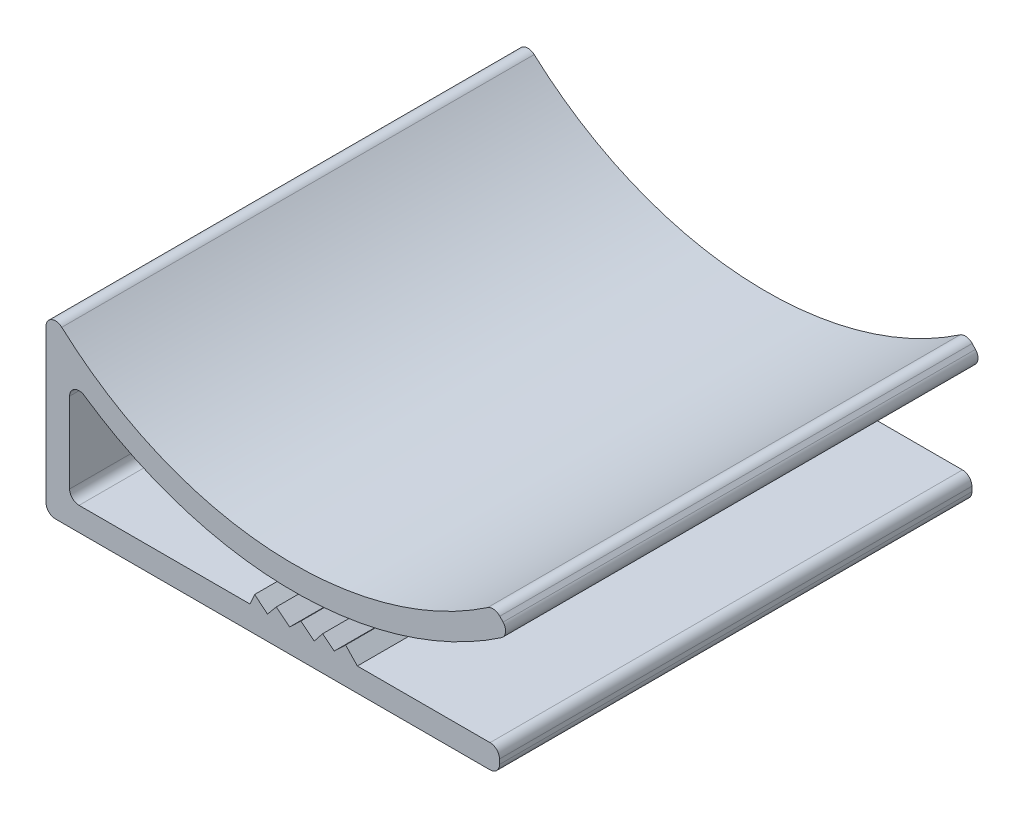
SolidWorks part; units mm, degrees
ref_plane "Alzado" through (0, 0, 0) normal (0, 0, 1) x (1, 0, 0)
ref_plane "Planta" through (0, 0, 0) normal (0, 1, 0) x (1, 0, 0)
ref_plane "Vista lateral" through (0, 0, 0) normal (1, 0, 0) x (0, 0, -1)
sketch "Croquis1" plane through (0, 0, 0) normal (0, 0, 1) x (1, 0, 0)
  line L0 (0.5, 0) -> (23.5, 0)
  line L1 (0, 0.5) -> (0, 8.5807)
  line L2 (1.75, 1.25) -> (10.798, 1.25)
  line L3 (1.25, 1.75) -> (1.25, 6.0049)
  line L4 (24, 0.5) -> (24, 0.75)
  line L6 (24.1885, 7.1165) -> (24.016, 7.3015)
  line L15 (10.798, 1.25) -> (11.0427, 1.8123)
  line L16 (11.0427, 1.8123) -> (11.7206, 1.25)
  line L17 (11.7206, 1.25) -> (12.187, 1.8123)
  line L18 (12.187, 1.8123) -> (12.8969, 1.25)
  line L19 (12.8969, 1.25) -> (13.4851, 1.8123)
  line L20 (13.4851, 1.8123) -> (14.195, 1.25)
  line L21 (14.195, 1.25) -> (14.6404, 1.8123)
  line L22 (14.6404, 1.8123) -> (15.2551, 1.3253)
  line L23 (15.2551, 1.3253) -> (15.8563, 1.9001)
  line L24 (15.8563, 1.9001) -> (16.4778, 1.25)
  line L25 (16.4778, 1.25) -> (23.5, 1.25)
  line L26 (1.25, 1.25) -> (24, 1.25) construction
  line L27 (0, 0) -> (24, 0) construction
  line L28 (1.25, 1.25) -> (1.25, 6.984) construction
  line L29 (0, 0) -> (0, 9.7555) construction
  arc A0 (0.8351, 8.9518) -> (23.3701, 7.3747) centre (13.1088, 22.5407) ccw
  arc A1 (2.0331, 6.4171) -> (10.1801, 3.1999) centre (13.1088, 22.5407) ccw
  arc A2 (10.1801, 3.1999) -> (24.1038, 6.362) centre (13.1088, 22.5407) ccw
  arc A3 (1.25, 6.984) -> (24.5688, 6.6879) centre (13.1088, 22.5407) ccw construction
  arc A4 (23.5, 0) -> (24, 0.5) centre (23.5, 0.5) ccw
  arc A5 (1.75, 1.25) -> (1.25, 1.75) centre (1.75, 1.75) cw
  arc A6 (0.5, 0) -> (0, 0.5) centre (0.5, 0.5) cw
  arc A7 (24.1038, 6.362) -> (24.1885, 7.1165) centre (23.8228, 6.7755) ccw
  arc A8 (0, 9.7555) -> (23.8365, 7.701) centre (13.1088, 22.5407) ccw construction
  arc A9 (23.3701, 7.3747) -> (24.016, 7.3015) centre (23.6503, 6.9606) cw
  arc A10 (1.25, 6.0049) -> (2.0331, 6.4171) centre (1.75, 6.0049) cw
  arc A11 (0, 8.5807) -> (0.8351, 8.9518) centre (0.5, 8.5807) cw
  arc A12 (23.5, 1.25) -> (24, 0.75) centre (23.5, 0.75) cw
  point P35 (24, 0)
  dimension "D4" = 0.5
  dimension "D1" = 0.5
  dimension "D3" = 1.25
extrude "Saliente-Extruir1" add sketch "Croquis1" along normal blind 25
ref_plane "Plane1" through (3.25, 0, 0) normal (1, 0, 0) x (0, 0, -1)
ref_plane "Plane2" through (0, 3.25, 0) normal (0, 1, 0) x (1, 0, 0)
ref_axis "Axis1" through (3.25, 3.25, -1.25) along (0, 0, 1)
sketch "Sketch1" plane through (0, 0, 0) normal (0, 0, -1) x (-1, 0, 0)
  point P0 (-3.25, 3.25)
sketch "Sketch2" plane through (0, 0, 25) normal (0, 0, 1) x (1, 0, 0)
  point P0 (3.25, 3.25)
ref_axis "Axis2" through (0, 9.5347, 0) along (0, -1, 0)
